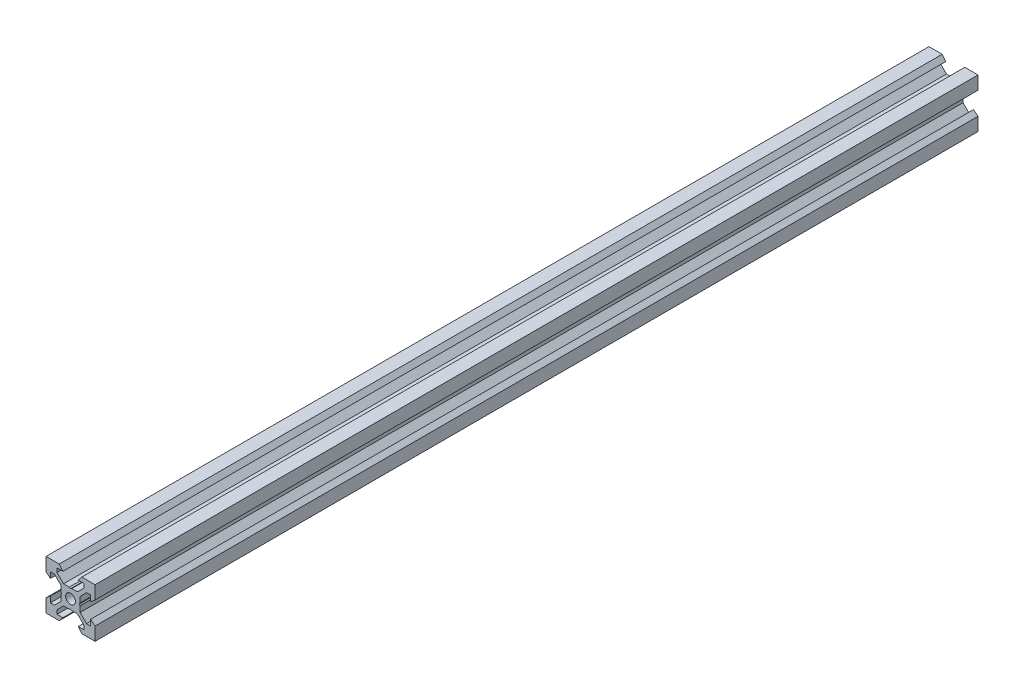
SolidWorks part; units mm, degrees
ref_plane "Front Plane" through (0, 0, 0) normal (0, 0, 1) x (1, 0, 0)
ref_plane "Top Plane" through (0, 0, 0) normal (0, 1, 0) x (1, 0, 0)
ref_plane "Right Plane" through (0, 0, 0) normal (1, 0, 0) x (0, 0, -1)
sketch "Sketch1" plane through (0, 0, 0) normal (0, 0, 1) x (1, 0, 0)
  line L0 (10, 10) -> (4.6104, 10) construction
  line L1 (10, 10) -> (10, 4.6104) construction
  line L2 (10, -10) -> (10, -4.6104) construction
  line L3 (10, -10) -> (4.6104, -10) construction
  line L4 (10, 10) -> (10, 4.6104)
  line L5 (6.5607, 5.5) -> (8.2, 5.5)
  line L6 (5.5, 8.2) -> (5.5, 6.5607)
  line L7 (10, 10) -> (4.6104, 10)
  line L8 (10, 10) -> (10, 4.6104)
  line L9 (6.5607, 5.5) -> (3.9, 2.8393)
  line L10 (5.5, 6.5607) -> (2.8393, 3.9)
  line L11 (10, 4.6104) -> (8.2, 3.1)
  line L12 (4.6104, 10) -> (3.1, 8.2)
  line L13 (8.2, 3.1) -> (8.2, 5.5)
  line L14 (3.1, 8.2) -> (5.5, 8.2)
  line L15 (-6.5607, 5.5) -> (-8.2, 5.5)
  line L16 (6.5607, -5.5) -> (8.2, -5.5)
  line L17 (3.1, -8.2) -> (5.5, -8.2)
  line L18 (8.2, -3.1) -> (8.2, -5.5)
  line L19 (4.6104, -10) -> (3.1, -8.2)
  line L20 (10, -4.6104) -> (8.2, -3.1)
  line L21 (0.5196, -3.9) -> (0, -3.6)
  line L22 (0.5196, 3.9) -> (0, 3.6)
  line L23 (3.6, 0) -> (3.9, -0.5196)
  line L24 (3.9, 0.5196) -> (3.6, 0)
  line L25 (3.9, 0.5196) -> (3.9, 2.8393)
  line L26 (2.8393, 3.9) -> (0.5196, 3.9)
  line L27 (3.9, -2.8393) -> (3.9, -0.5196)
  line L28 (2.8393, -3.9) -> (0.5196, -3.9)
  line L29 (5.5, -6.5607) -> (2.8393, -3.9)
  line L30 (6.5607, -5.5) -> (3.9, -2.8393)
  line L31 (10, -10) -> (10, -4.6104)
  line L32 (10, -10) -> (4.6104, -10)
  line L33 (5.5, -8.2) -> (5.5, -6.5607)
  line L34 (-6.5607, -5.5) -> (-8.2, -5.5)
  line L35 (10, -10) -> (10, -4.6104)
  line L36 (0, 0) -> (0, 8.2) construction
  line L37 (-10, -10) -> (-4.6104, -10) construction
  line L38 (-10, -10) -> (-10, -4.6104) construction
  line L39 (-10, 10) -> (-10, 4.6104) construction
  line L40 (-10, 10) -> (-4.6104, 10) construction
  line L41 (-10, -10) -> (-10, -4.6104)
  line L43 (-5.5, -8.2) -> (-5.5, -6.5607)
  line L44 (-10, -10) -> (-4.6104, -10)
  line L45 (-10, -10) -> (-10, -4.6104)
  line L46 (-6.5607, -5.5) -> (-3.9, -2.8393)
  line L47 (-5.5, -6.5607) -> (-2.8393, -3.9)
  line L48 (-2.8393, -3.9) -> (-0.5196, -3.9)
  line L49 (-3.9, -2.8393) -> (-3.9, -0.5196)
  line L50 (-2.8393, 3.9) -> (-0.5196, 3.9)
  line L51 (-3.9, 0.5196) -> (-3.9, 2.8393)
  line L52 (-3.9, 0.5196) -> (-3.6, 0)
  line L53 (-3.6, 0) -> (-3.9, -0.5196)
  line L54 (-0.5196, 3.9) -> (0, 3.6)
  line L55 (-0.5196, -3.9) -> (0, -3.6)
  line L56 (-10, -4.6104) -> (-8.2, -3.1)
  line L57 (-4.6104, -10) -> (-3.1, -8.2)
  line L58 (-8.2, -3.1) -> (-8.2, -5.5)
  line L59 (-3.1, -8.2) -> (-5.5, -8.2)
  line L60 (-10, -10) -> (10, -10) construction
  line L61 (-10, -10) -> (-10, 10) construction
  line L62 (-3.1, 8.2) -> (-5.5, 8.2)
  line L63 (-8.2, 3.1) -> (-8.2, 5.5)
  line L64 (-4.6104, 10) -> (-3.1, 8.2)
  line L65 (-10, 4.6104) -> (-8.2, 3.1)
  line L66 (-5.5, 6.5607) -> (-2.8393, 3.9)
  line L67 (-6.5607, 5.5) -> (-3.9, 2.8393)
  line L68 (-10, 10) -> (-10, 4.6104)
  line L69 (-10, 10) -> (-4.6104, 10)
  line L70 (-5.5, 8.2) -> (-5.5, 6.5607)
  line L71 (-10, 10) -> (10, 10) construction
  line L72 (-10, 10) -> (-10, 4.6104)
  line L73 (10, -10) -> (10, 10) construction
  line L74 (-10, -10) -> (10, 10) construction
  line L75 (-10, 10) -> (10, -10) construction
  circle A0 centre (0, 0) radius 2
  dimension "D7" = 4
  dimension "D1" = 20
  dimension "D2" = 5.3896
  dimension "D3" = 4.5
  dimension "D4" = 50
  dimension "D5" = 1.8
  dimension "D6" = 1.5104
  dimension "D8" = 5.5
  dimension "D9" = 120
  dimension "D10" = 0.3
  dimension "D11" = 2.3197
  dimension "D12" = 7.8
  dimension "D13" = 7.8
  dimension "D14" = 1.5
  dimension "D15" = 2.6607
extrude "Boss-Extrude1" add sketch "Sketch1" along normal mid plane 360 contours L70 L62 L64 L69 L68 L65 L63 L15 L67 L51 L52 L53 L49 L46 L34 L58 L56 L41 L44 L57 L59 L43 L47 L48 L55 L21 L28 L29 L33 L17 L19 L32 L31 L20 L18 L16 L30 L27 L23 L24 L25 L9 L5 L13 L11 L4 L7 L12 L14 L6 L10 region at (9.7172, 7.3052, 0)
